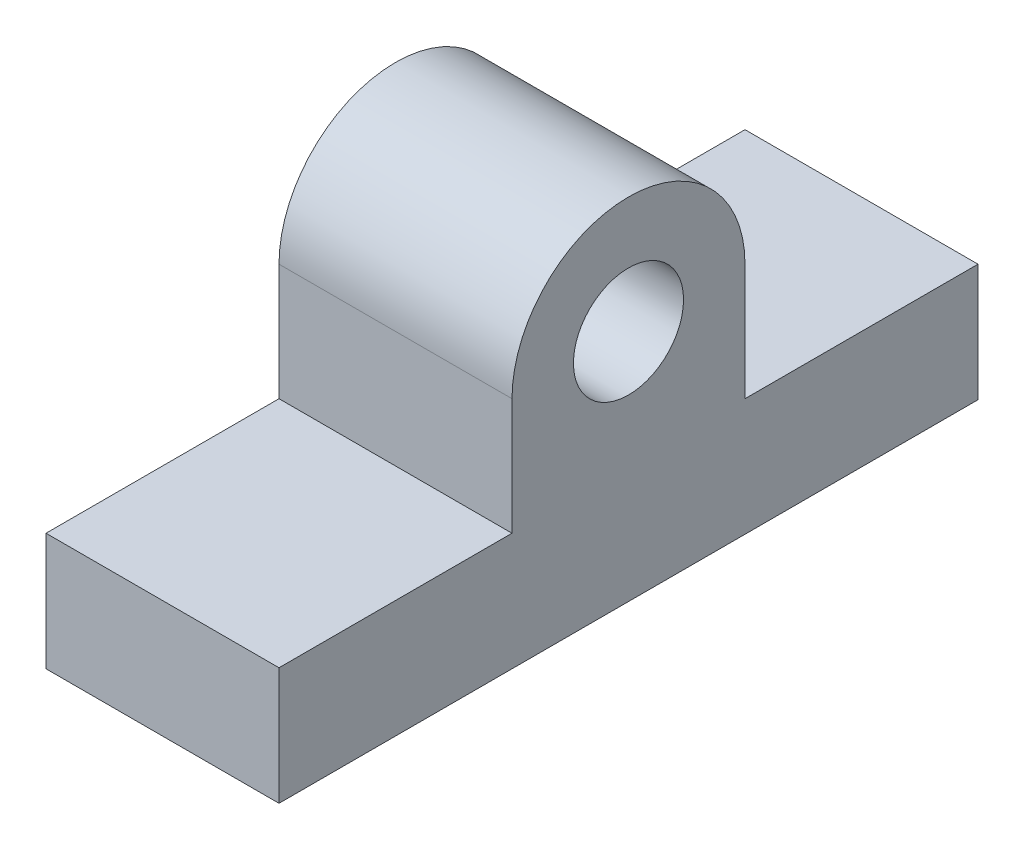
SolidWorks part; units mm, degrees
ref_plane "Front Plane" through (0, 0, 0) normal (0, 0, 1) x (1, 0, 0)
ref_plane "Top Plane" through (0, 0, 0) normal (0, 1, 0) x (1, 0, 0)
ref_plane "Right Plane" through (0, 0, 0) normal (1, 0, 0) x (0, 0, -1)
sketch "Sketch1" plane through (0, 0, 0) normal (1, 0, 0) x (0, 0, -1)
  line L0 (12.7, 0) -> (12.7, -12.7)
  line L1 (38.1, -12.7) -> (38.1, -25.5)
  line L2 (38.1, -25.5) -> (-38.1, -25.5)
  line L3 (-38.1, -25.5) -> (-38.1, -12.7)
  line L4 (12.7, -12.7) -> (38.1, -12.7)
  line L5 (-12.7, 0) -> (-12.7, -12.7)
  line L6 (-12.7, -12.7) -> (-38.1, -12.7)
  arc A0 (12.7, 0) -> (-12.7, 0) centre (0, 0) ccw
  dimension "D1" = 25.4
  dimension "D2" = 25.4
  dimension "D3" = 25.4
  dimension "D4" = 12.8
  dimension "D5" = 12.8
  dimension "D6" = 12.7
extrude "Boss-Extrude1" add sketch "Sketch1" along normal blind 25.4
sketch "Sketch2" plane through (25.4, 0, 0) normal (1, 0, 0) x (0, 0, -1)
  circle A0 centre (0, 0) radius 6
  dimension "D1" = 12
extrude "Cut-Extrude1" cut sketch "Sketch2" against normal through all
